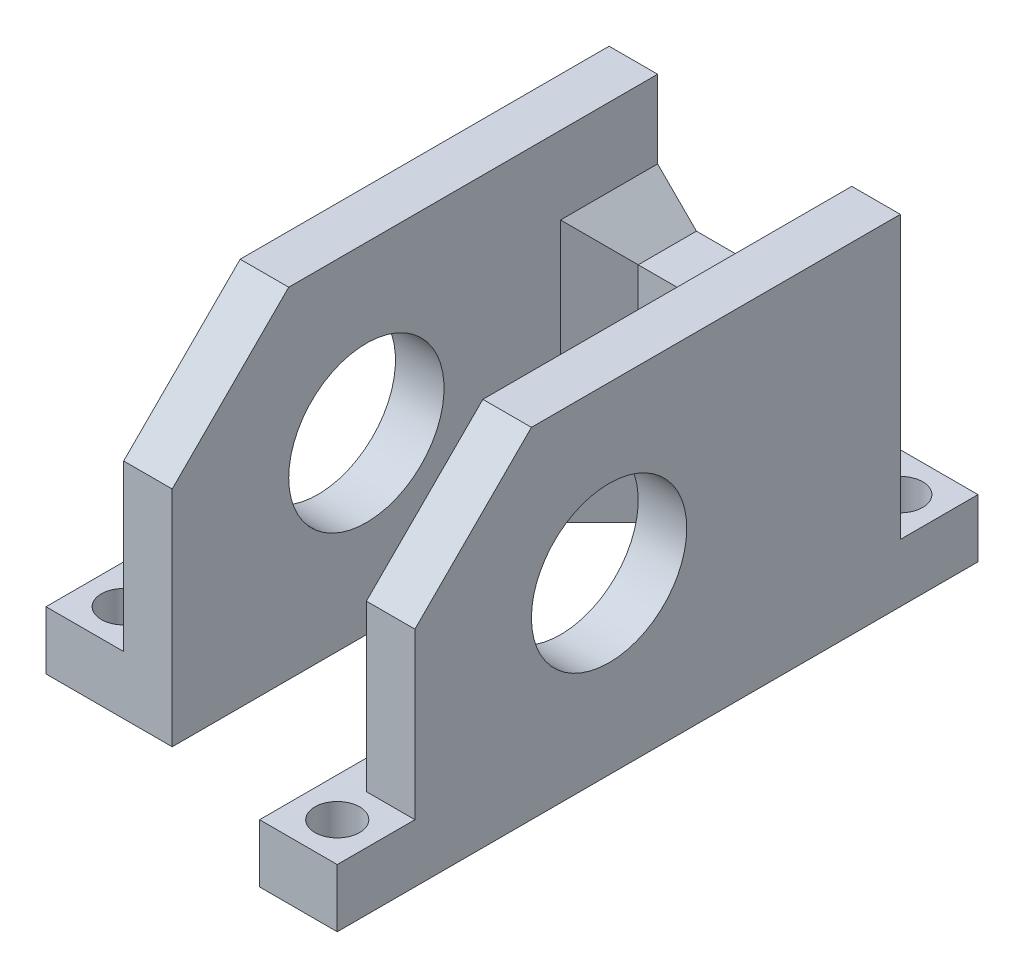
SolidWorks part; units mm, degrees
ref_plane "Plan de face" through (0, 0, 0) normal (0, 0, 1) x (1, 0, 0)
ref_plane "Plan de dessus" through (0, 0, 0) normal (0, 1, 0) x (1, 0, 0)
ref_plane "Plan de droite" through (0, 0, 0) normal (1, 0, 0) x (0, 0, -1)
sketch "Esquisse1" plane through (0, 0, 0) normal (0, 1, 0) x (1, 0, 0)
  line L8 (-23, 9) -> (-23, -41)
  line L9 (-18, 9) -> (-23, 9)
  line L28 (-23, -41) -> (-18, -41)
  line L30 (-18, -41) -> (-18, 3)
  line L31 (7, 3) -> (7, -41)
  line L32 (7, -41) -> (2, -41)
  line L33 (2, -41) -> (2, 3)
  line L35 (-18, 9) -> (2, 9)
  line L38 (-18, 3) -> (2, 3)
  line L39 (-23, -41) -> (-31, -41)
  line L40 (-31, -41) -> (-31, -33)
  line L45 (7, 9) -> (7, 3)
  line L46 (7, 3) -> (-23, 3) construction
  line L47 (-23, 3) -> (-23, 9)
  line L50 (-31, -33) -> (-23, -33)
  line L51 (2, 9) -> (7, 9)
  line L55 (-31, -33) -> (-23, -41) construction
  line L56 (-23, -33) -> (-31, -41) construction
  line L57 (-23, 9) -> (-31, 9)
  line L58 (7, 9) -> (7, 17)
  line L59 (7, 17) -> (-1, 17)
  line L60 (-1, 17) -> (-1, 9)
  line L61 (-1, 9) -> (7, 17) construction
  line L62 (-1, 17) -> (7, 9) construction
  line L63 (7, -41) -> (7, -49)
  line L64 (7, -49) -> (-1, -49)
  line L65 (-1, -49) -> (-1, -37)
  line L66 (-1, -37) -> (2, -37)
  line L67 (7, -49) -> (-1, -41) construction
  line L68 (-1, -41) -> (-1, -49) construction
  line L69 (7, -41) -> (-1, -49) construction
  line L70 (-31, 9) -> (-31, 1)
  line L71 (-31, 1) -> (-23, 1)
  line L72 (-31, 9) -> (-23, 1) construction
  line L73 (-23, 1) -> (-23, 9) construction
  line L74 (-31, 1) -> (-23, 9) construction
  circle A8 centre (3, 13) radius 2.3
  circle A10 centre (3, -45) radius 2.3
  circle A11 centre (-27, -37) radius 2.3
  circle A12 centre (-27, 5) radius 2.3
extrude "Boss.-Extru.1" add sketch "Esquisse1" along normal blind 35 contours L46 | L46 L9 | L46 L35 | L51 L46 region at (-20.5, 0, -8.4169)
extrude "Boss.-Extru.7" add sketch "Esquisse1<6>" along normal blind 8 contours L28 region at (-20.5, 0, -8.4169)
sketch "Esquisse1<6>" plane through (0, 0, 0) normal (0, 1, 0) x (1, 0, 0) same geometry as "Esquisse1"
extrude "Boss.-Extru.8" add sketch "Esquisse1<8>" along normal blind 6 contours L59 L60 L35 L51 L58 A8 | L30 L28 L40 | L66 L65 L64 L63 L32 L33 A10 | L50 L40 L39 L8 A11 | L70 L71 L8 L57 A12 region at (-23.1131, 0, -6) region at (-0.8869, 0, -13) region at (-23.1131, 0, 37) region at (6.8558, 0, 45)
sketch "Esquisse1<8>" plane through (0, 0, 0) normal (0, 1, 0) x (1, 0, 0) same geometry as "Esquisse1"
sketch "Esquisse6" plane through (0, 0, 0) normal (0, -1, 0) x (1, 0, 0)
  line L0 (-18, -3) -> (-14, -3)
  line L1 (-18, -3) -> (2, -3) construction
  line L2 (-18, -3) -> (-18, 1)
  line L3 (-18, 41) -> (-18, -3) construction
  line L4 (-18, 1) -> (-14, -3)
  line L5 (2, -3) -> (-2, -3)
  line L6 (-2, -3) -> (2, 1)
  line L7 (2, 37) -> (2, -3) construction
  line L8 (2, 1) -> (2, -3)
extrude "Boss.-Extru.9" add sketch "Esquisse6" against normal blind 35
sketch "Esquisse7" plane through (0, 0, -9) normal (0, 0, -1) x (-1, 0, 0)
  line L0 (-7, 35) -> (-2, 35) construction
  line L3 (18, 23) -> (14, 23) construction
  line L8 (-2, 23) -> (2, 23) construction
  line L9 (2, 23) -> (-2, 23) construction
  line L10 (-2, 23) -> (-2, 27) construction
  line L14 (-2, 35) -> (18, 35)
  line L16 (18, 23) -> (18, 27) construction
  line L17 (2, 23) -> (14, 23)
  line L18 (-2, 27) -> (2, 23)
  line L24 (-2, 27) -> (-2, 35)
  line L25 (18, 23) -> (18, 35)
  line L26 (18, 27) -> (14, 23)
  line M8 (23, 35) -> (-7, 35)
extrude "Enlèv. mat.-Extru.5" cut sketch "Esquisse7" against normal blind 35 contours L18 M8 region at (-8, 29.3333, -9)
sketch "Esquisse8" plane through (-23, 0, 0) normal (-1, 0, 0) x (0, 0, 1)
  line L0 (41, 0) -> (21, 0) construction
  line L1 (-1, 0) -> (33, 0) construction
  line L2 (21, 0) -> (21, 18) construction
  line L3 (41, 35) -> (41, 23)
  line L4 (41, 35) -> (41, 6) construction
  line L5 (41, 23) -> (41, 35)
  line L6 (41, 35) -> (29, 35)
  line L7 (-9, 35) -> (41, 35) construction
  line L8 (29, 35) -> (41, 23)
  circle A0 centre (21, 18) radius 8
  line M3 (41, 6) -> (41, 35)
  line M4 (41, 35) -> (-9, 35)
extrude "Enlèv. mat.-Extru.6" cut sketch "Esquisse8" against normal blind 50 contours A0 | L8 M4 M3 region at (-23, 31, 37) region at (-23, 18, 21)
